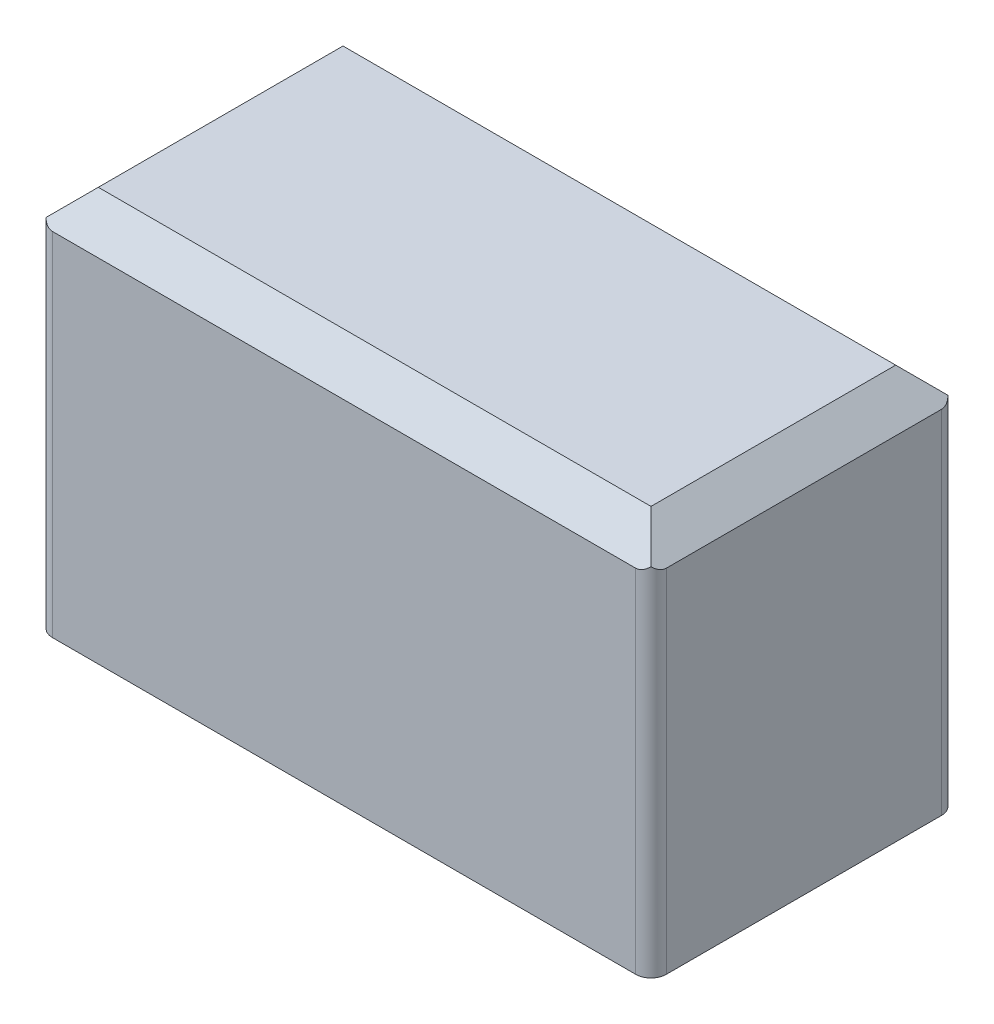
SolidWorks part; units mm, degrees
material "PBT General Purpose"
ref_plane "Front Plane" through (0, 0, 0) normal (0, 0, 1) x (1, 0, 0)
ref_plane "Top Plane" through (0, 0, 0) normal (0, 1, 0) x (1, 0, 0)
ref_plane "Right Plane" through (0, 0, 0) normal (1, 0, 0) x (0, 0, -1)
sketch "Sketch1" plane through (0, 0, 0) normal (0, 1, 0) x (1, 0, 0)
  line L1 (0, 0) -> (52, 0)
  line L2 (0, 0) -> (0, 20)
  line L3 (0, 20) -> (52, 20)
  line L4 (52, 0) -> (52, 20)
  dimension "D1" = 52
  dimension "D2" = 20
extrude "Boss-Extrude1" add sketch "Sketch1" along normal blind 25
chamfer "Chamfer1" distance 2 angle 45 4 edges at (26, 25, -20) (52, 25, -10) (26, 25, 0) (0, 25, -10)
fillet "Fillet1" radius 1 4 edges at (0, 11.5, 0) (0, 11.5, -20) (52, 11.5, -20) (52, 11.5, 0)
sketch "Sketch2" plane through (0, 0, 0) normal (0, -1, 0) x (1, 0, 0)
  line L0 (1, 0) -> (51, 0) construction
  line L1 (40.1398, 0) -> (52.1143, 0)
  line L2 (40.1398, 0) -> (40.1398, -20.6951)
  line L3 (40.1398, -20.6951) -> (52.1143, -20.6951)
  line L4 (52.1143, 0) -> (52.1143, -20.6951)
extrude "Cut-Extrude1" cut sketch "Sketch2" against normal blind 40
fillet "Fillet2" radius 1 2 edges at (40.1398, 11.5, 0) (40.1398, 11.5, -20)
chamfer "Chamfer5" distance 2 angle 45 1 edges at (40.1398, 25, -10)
